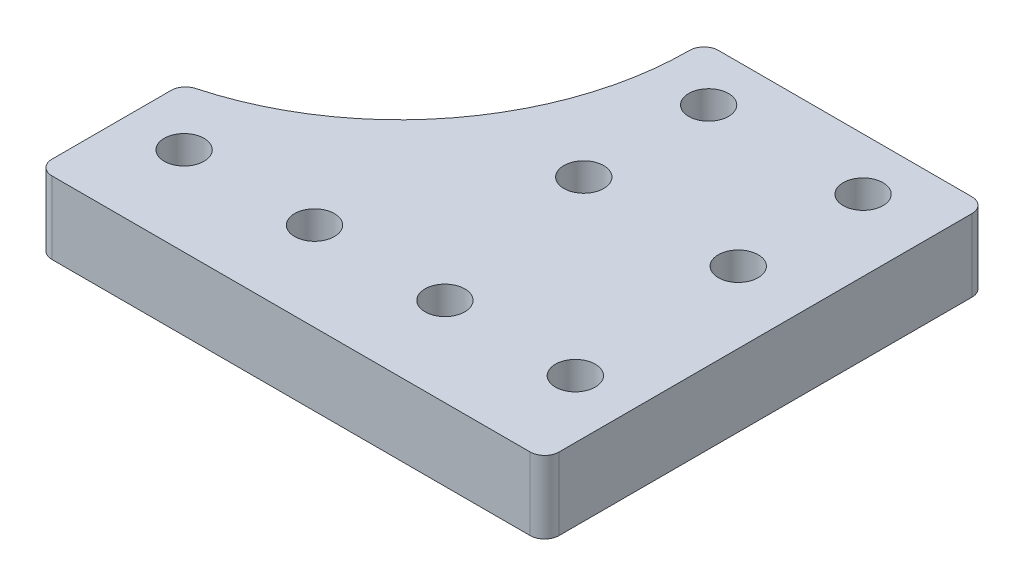
SolidWorks part; units mm, degrees
ref_plane "Front Plane" through (0, 0, 0) normal (0, 0, 1) x (1, 0, 0)
ref_plane "Top Plane" through (0, 0, 0) normal (0, 1, 0) x (1, 0, 0)
ref_plane "Right Plane" through (0, 0, 0) normal (1, 0, 0) x (0, 0, -1)
sketch "Sketch1" plane through (0, 0, 0) normal (0, 1, 0) x (1, 0, 0)
  line L1 (0, 0) -> (-70, 0)
  line L2 (0, 0) -> (0, 61)
  line L5 (-70, 20) -> (-70, 0)
  line L6 (-70, 20) -> (-39, 20)
  line L7 (-39, 20) -> (-39, 61)
  line L8 (-39, 61) -> (0, 61)
  line L9 (-39, 61) -> (0, 61)
  dimension "D1" = 31
  dimension "D2" = 39
  dimension "D3" = 20
  dimension "D4" = 61
extrude "Boss-Extrude2" add sketch "Sketch1" along normal blind 10 contours L8 L7 L6 L5 L1 L2 region at (-26.7357, 0, -26.2619)
fillet "Fillet4" radius 40 1 edges at (-39, 5, -20)
fillet "Fillet5" radius 2 3 edges at (0, 5, 0) (-70, 5, 0) (0, 5, -61)
fillet "Fillet6" radius 2 1 edges at (-39, 5, -61)
fillet "Fillet7" radius 2 1 edges at (-70, 5, -20)
sketch "Sketch2" plane through (0, 10, 0) normal (0, 1, 0) x (1, 0, 0)
  line L0 (0, 2) -> (0, 59) construction
  line L1 (-70, 18.4404) -> (-70, 2) construction
  circle A0 centre (-9.8379, 53.7989) radius 2.75
  circle A1 centre (-31.1596, 53.7989) radius 2.75
  circle A2 centre (-31.1596, 36.568) radius 2.75
  circle A3 centre (-9.8379, 36.568) radius 2.75
  circle A4 centre (-8, 12.2411) radius 2.75
  circle A5 centre (-26, 12.2411) radius 2.75
  circle A6 centre (-44, 12.2411) radius 2.75
  circle A7 centre (-62, 12.2411) radius 2.75
  point P16 (0, 0)
  point P17 (0, 0)
  point P18 (0, 0)
  point P19 (0, 0)
  point P20 (0, 0)
  point P23 (0, 0)
  dimension "D1" = 5.5
  dimension "D2" = 5.5
  dimension "D3" = 5.5
  dimension "D4" = 5.5
  dimension "D5" = 5.5
  dimension "D6" = 5.5
  dimension "D7" = 5.5
  dimension "D8" = 5.5
  dimension "D9" = 8
  dimension "D10" = 8
  dimension "D11" = 18
  dimension "D12" = 18
extrude "Cut-Extrude1" cut sketch "Sketch2" against normal through all
